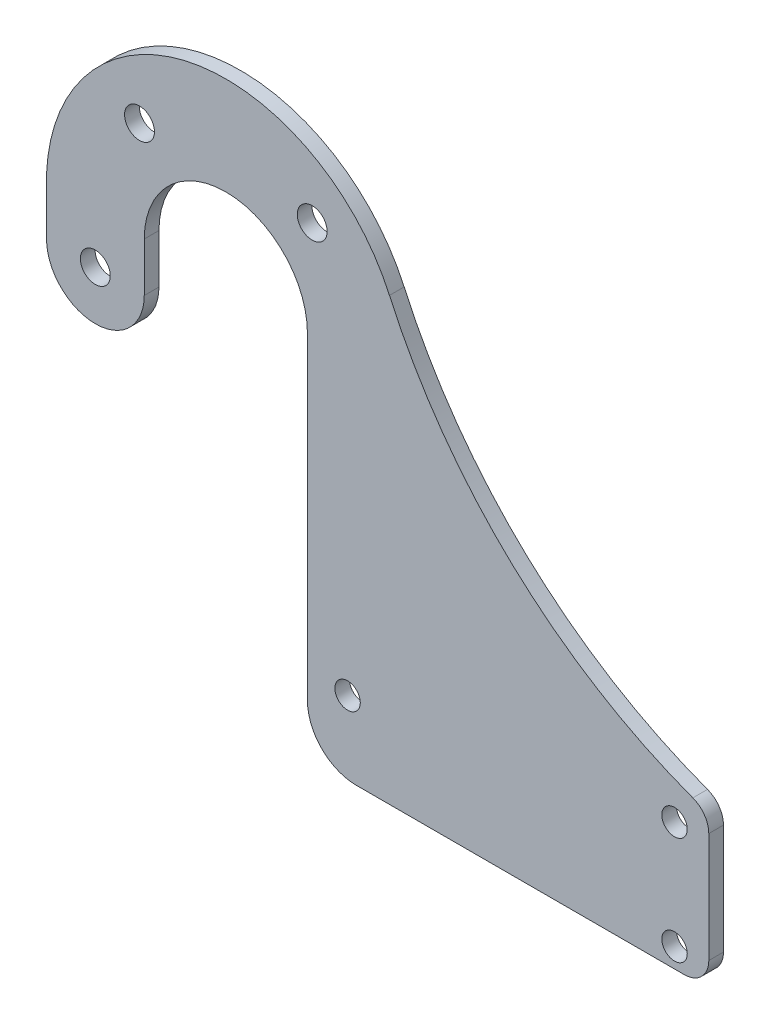
SolidWorks part; units mm, degrees
material "7075-T6, Chapa (SS)"
ref_plane "Plano frontal" through (0, 0, 0) normal (0, 0, 1) x (1, 0, 0)
ref_plane "Plano superior" through (0, 0, 0) normal (0, 1, 0) x (1, 0, 0)
ref_plane "Plano direito" through (0, 0, 0) normal (1, 0, 0) x (0, 0, -1)
sketch "Esboço1" plane through (0, 0, 0) normal (0, 0, 1) x (1, 0, 0)
  line L8 (-82, 31) -> (-82, 75)
  line L9 (-62, 75) -> (-62, 31)
  line L10 (0, 0) -> (0, 31)
  line L11 (0, 31) -> (-82, 31)
  line L12 (-82, 0) -> (0, 0)
  line L13 (-82, 0) -> (-82, 31)
  line L14 (-115.3375, 75) -> (-135.3056, 63.4714)
  line L15 (-135.3056, 63.4714) -> (-135.3056, 73.4714)
  circle A4 centre (-73.8, 15) radius 2.6
  arc A5 (-115.3375, 75) -> (-82, 75) centre (-98.6688, 75) cw
  circle A6 centre (-7, 4) radius 2.6
  circle A7 centre (-7, 26) radius 2.6
  arc A9 (-62, 75) -> (-135.3056, 73.4714) centre (-98.6688, 75) ccw
  point P2 (-64.8427, 70.4022)
  point P3 (-62, 31)
  dimension "D4" = 7
  dimension "D5" = 5.2
  dimension "D7" = 36.6687
  dimension "D8" = 60
  dimension "D11" = 15
  dimension "D13" = 16.6687
  dimension "D1" = 31
  dimension "D2" = 22
  dimension "D3" = 4
  dimension "D6" = 82
  dimension "D9" = 60
  dimension "D10" = 10
  dimension "D12" = 8.2
extrude "Ressalto-extrusão1" add sketch "Esboço1" along normal blind 3
fillet "Filete2" radius 110 1 edges at (-62, 31, 1.5)
fillet "Filete3" radius 4 1 edges at (-135.3056, 63.4714, 1.5)
sketch "Esboço2" plane through (0, 0, 3) normal (0, 0, 1) x (1, 0, 0)
  line L0 (-135.3056, 70.3996) -> (-135.3056, 55)
  line L1 (-135.3056, 55) -> (-115.3375, 55)
  line L2 (-115.3375, 55) -> (-115.3375, 75)
  line L9 (-129.3056, 66.9355) -> (-115.3375, 75)
  line L10 (-82, 75) -> (-82, 0)
  line L12 (-82, 0) -> (0, 0)
  line L13 (0, 0) -> (0, 31)
  line L14 (-135.3056, 73.4714) -> (-135.3056, 70.3996)
  line L15 (-129.3056, 66.9355) -> (-115.3375, 75)
  line L16 (-82, 75) -> (-82, 0)
  line L18 (-82, 0) -> (0, 0)
  line L19 (0, 0) -> (0, 31)
  line L20 (-135.3056, 73.4714) -> (-135.3056, 70.3996)
  arc A3 (-82, 75) -> (-115.3375, 75) centre (-98.6688, 75) ccw
  arc A4 (-82, 75) -> (-115.3375, 75) centre (-98.6688, 75) ccw
  arc A6 (-65.2388, 90.0676) -> (0, 31) centre (35.0455, 135.268) ccw
  arc A7 (-65.2388, 90.0676) -> (0, 31) centre (35.0455, 135.268) ccw
  arc A12 (-65.2388, 90.0676) -> (-135.3056, 73.4714) centre (-98.6688, 75) ccw
  arc A13 (-135.3056, 70.3996) -> (-129.3056, 66.9355) centre (-131.3056, 70.3996) ccw
  arc A19 (-65.2388, 90.0676) -> (-135.3056, 73.4714) centre (-98.6688, 75) ccw
  arc A20 (-135.3056, 70.3996) -> (-129.3056, 66.9355) centre (-131.3056, 70.3996) ccw
  point P6 (0, 0)
  point P7 (-115.3375, 53.4714)
  point P12 (0, 0)
  point P14 (0, 0)
  point P15 (0, 0)
  point P16 (0, 0)
  point P17 (0, 0)
  point P18 (-115.3375, 34.3359)
  dimension "D2" = 20
  dimension "D1" = 0
extrude "Ressalto-extrusão2" add sketch "Esboço2" against normal through all
fillet "Filete4" radius 10 2 edges at (-135.3056, 55, 1.5) (-115.3375, 55, 1.5)
fillet "Filete5" radius 10 1 edges at (-82, 0, 1.5)
fillet "Filete6" radius 5 2 edges at (0, 0, 1.5) (0, 31, 1.5)
sketch "Esboço3" plane through (0, 0, 3) normal (0, 0, 1) x (1, 0, 0)
  line L0 (-125.3375, 75) -> (-125.3375, 65) construction
  line L1 (-98.6688, 91.6687) -> (-98.6688, 111.6687) construction
  arc A1 (-125.3375, 75) -> (-72, 75) centre (-98.6688, 75) cw construction
  arc A4 (-65.2388, 90.0676) -> (-135.3056, 73.4714) centre (-98.6688, 75) ccw construction
  arc A12 (-65.2388, 90.0676) -> (-135.3056, 73.4714) centre (-98.6688, 75) ccw construction
  arc A13 (-65.2388, 90.0676) -> (-135.3056, 73.4714) centre (-98.6688, 75) ccw
  arc A18 (-82, 75) -> (-115.3375, 75) centre (-98.6688, 75) ccw construction
  circle A21 centre (-125.3375, 65) radius 3.05
  circle A22 centre (-116.3102, 95) radius 3.05
  circle A23 centre (-81.0273, 95) radius 3.05
  point P0 (-125.3056, 65)
  point P1 (0, 0)
  point P5 (-98.6688, 101.6687)
  point P16 (-98.6688, 111.6687)
  dimension "D1" = 6.1
  dimension "D3" = 30
extrude "Corte-extrusão1" cut sketch "Esboço3" against normal blind 10
